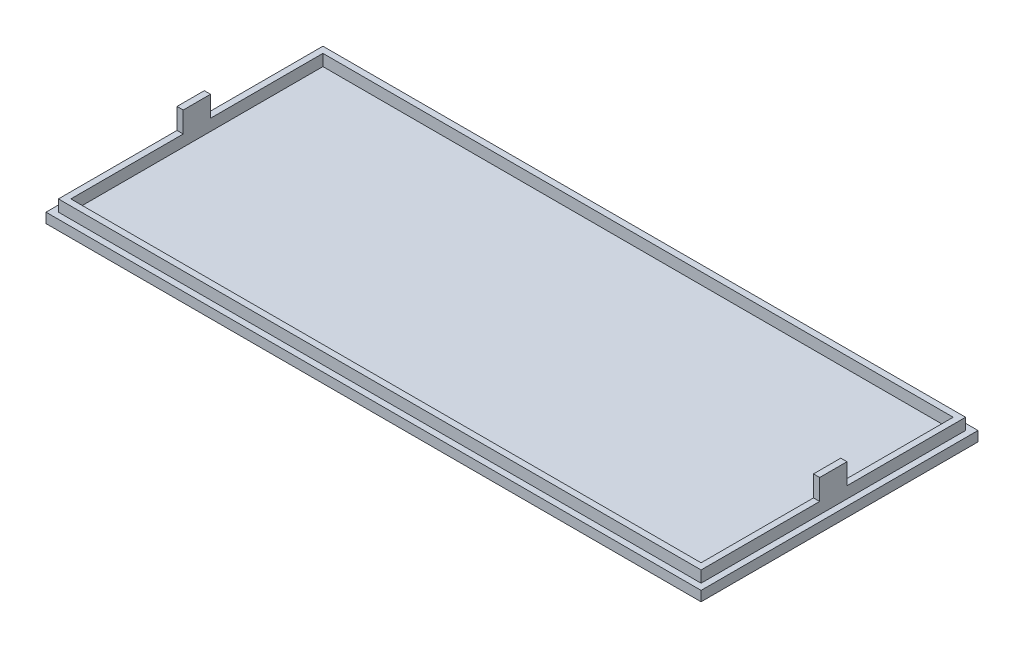
SolidWorks part; units mm, degrees
material "ABS PC"
ref_plane "Front Plane" through (0, 0, 0) normal (0, 0, 1) x (1, 0, 0)
ref_plane "Top Plane" through (0, 0, 0) normal (0, 1, 0) x (1, 0, 0)
ref_plane "Right Plane" through (0, 0, 0) normal (1, 0, 0) x (0, 0, -1)
sketch "Sketch1" plane through (0, 0, 0) normal (0, 1, 0) x (1, 0, 0)
  line L0 (-27.9, -7.9454) -> (-26.9, -7.9454) construction
  line L1 (-28.9, 14.3746) -> (76.7, 14.3746)
  line L2 (-28.9, 14.3746) -> (-28.9, -30.2654)
  line L3 (-28.9, -30.2654) -> (76.7, -30.2654)
  line L4 (76.7, 14.3746) -> (76.7, -30.2654)
  line L5 (-27.9, 13.3746) -> (75.7, 13.3746)
  line L6 (-27.9, 13.3746) -> (-27.9, -29.2654)
  line L7 (-27.9, -29.2654) -> (75.7, -29.2654)
  line L8 (75.7, 13.3746) -> (75.7, -29.2654)
  line L9 (-26.9, 12.3746) -> (74.7, 12.3746)
  line L10 (-26.9, 12.3746) -> (-26.9, -28.2654)
  line L11 (-26.9, -28.2654) -> (74.7, -28.2654)
  line L12 (74.7, 12.3746) -> (74.7, -28.2654)
  line L13 (-27.9, -5.7454) -> (-26.9, -5.7454)
  line L14 (-27.9, -10.1454) -> (-26.9, -10.1454)
  line L15 (74.7, -7.9454) -> (75.7, -7.9454) construction
  line L16 (74.7, -5.7454) -> (75.7, -5.7454)
  line L17 (74.7, -10.1454) -> (75.7, -10.1454)
  dimension "D1" = 44.64
  dimension "D2" = 105.6
  dimension "D3" = 1
  dimension "D4" = 1
  dimension "D5" = 1
  dimension "D6" = 1
  dimension "D7" = 1
  dimension "D8" = 1
  dimension "D9" = 1
  dimension "D10" = 1
  dimension "D11" = 2.2
  dimension "D12" = 2.2
  dimension "D13" = 2.2
  dimension "D14" = 2.2
extrude "Boss-Extrude1" add sketch "Sketch1" along normal blind 1.6 contours L4 L1 L2 L3 L5 L8 L7 L6 | L17 L12 L11 L10 L14 L6 L7 L8 | L6 L14 L10 L13 | L12 L16 L8 L5 L6 L13 L10 L9 | L12 L9 L10 L11 | L12 L17 L8 L16 region at (23.9, 0, -14.2599) region at (23.9, 0, -13.2692) region at (-27.4, 0, 7.9454) region at (75.2, 0, 7.9454) region at (-27.4, 0, 11.1989) region at (23.9, 0, 7.9454)
extrude "Boss-Extrude2" add sketch "Sketch1<3>" along normal blind 3.45 contours L12 L16 L8 L5 L6 L13 L10 L9 | L17 L12 L11 L10 L14 L6 L7 L8 | L6 L14 L10 L13 | L12 L17 L8 L16 region at (23.9, 0, -13.2692) region at (-27.4, 0, 7.9454) region at (75.2, 0, 7.9454) region at (-27.4, 0, 11.1989)
sketch "Sketch1<3>" plane through (0, 0, 0) normal (0, 1, 0) x (1, 0, 0) same geometry as "Sketch1"
extrude "Boss-Extrude3" add sketch "Sketch1<4>" along normal blind 6.8 contours L12 L17 L8 L16 | L6 L14 L10 L13 region at (-27.4, 0, 7.9454) region at (75.2, 0, 7.9454)
sketch "Sketch1<4>" plane through (0, 0, 0) normal (0, 1, 0) x (1, 0, 0) same geometry as "Sketch1"
